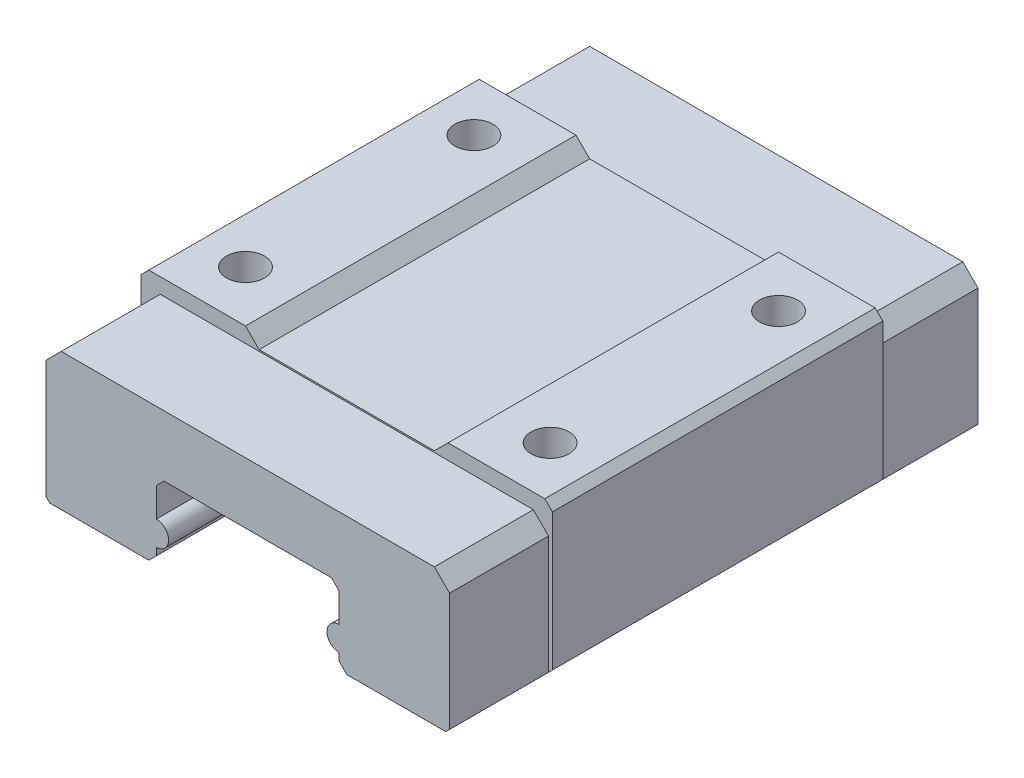
SolidWorks part; units mm, degrees
material "1023 Carbon Steel Sheet (SS)"
ref_plane "Front Plane" through (0, 0, 0) normal (0, 0, 1) x (1, 0, 0)
ref_plane "Top Plane" through (0, 0, 0) normal (0, 1, 0) x (1, 0, 0)
ref_plane "Right Plane" through (0, 0, 0) normal (1, 0, 0) x (0, 0, -1)
sketch "Master Sketch" plane through (0, 0, 0) normal (0, 1, 0) x (1, 0, 0)
  line L0 (-10, -7.5) -> (10, 7.5) construction
  line L1 (-13.25, -17.35) -> (13.25, -17.35)
  line L2 (-13.25, -17.35) -> (-13.25, 17.35)
  line L3 (-13.25, 17.35) -> (13.25, 17.35)
  line L4 (13.25, -17.35) -> (13.25, 17.35)
  line L5 (-13.25, -17.35) -> (13.25, 17.35) construction
  line L6 (-13.25, 17.35) -> (13.25, -17.35) construction
  line L7 (-13.5, -10.85) -> (13.5, -10.85)
  line L8 (-13.5, -10.85) -> (-13.5, 10.85)
  line L9 (-13.5, 10.85) -> (13.5, 10.85)
  line L10 (13.5, -10.85) -> (13.5, 10.85)
  line L11 (-13.5, -10.85) -> (13.5, 10.85) construction
  line L12 (-13.5, 10.85) -> (13.5, -10.85) construction
  point P0 (0, 0)
  point P5 (0, 0)
  point P11 (10, 7.5)
  point P12 (-10, 7.5)
  point P13 (10, -7.5)
  point P14 (-10, -7.5)
  dimension "D1" = 26.5
  dimension "D2" = 34.7
  dimension "D3" = 21.7
  dimension "D4" = 15
  dimension "D5" = 20
  dimension "D6" = 27
ref_plane "BlockMaxHeightPlane" through (0, 10, 0) normal (0, 1, 0) x (1, 0, 0)
sketch "MainBlockSketch" plane through (0, 0, 0) normal (0, 1, 0) x (1, 0, 0)
  line L0 (-13.25, -17.35) -> (13.25, -17.35) construction
  line L1 (13.25, -17.35) -> (13.25, 17.35) construction
  line L2 (-13.25, 17.35) -> (13.25, 17.35) construction
  line L3 (-13.25, -17.35) -> (-13.25, 17.35) construction
  line L4 (-13.25, -17.35) -> (13.25, -17.35)
  line L5 (13.25, -17.35) -> (13.25, 17.35)
  line L6 (-13.25, 17.35) -> (13.25, 17.35)
  line L7 (-13.25, -17.35) -> (-13.25, 17.35)
extrude "MainBlock" add sketch "MainBlockSketch" along normal blind 9
sketch "FacedSurfaceSketch" plane through (0, 0, 0) normal (0, 1, 0) x (1, 0, 0)
  line L0 (-13.5, -10.85) -> (13.5, -10.85) construction
  line L3 (-13.5, 10.85) -> (13.5, 10.85) construction
  line L4 (-13.5, -10.85) -> (13.5, -10.85)
  line L7 (-13.5, 10.85) -> (13.5, 10.85)
  line L8 (-13.5, 10.85) -> (-13.5, -10.85)
  line L9 (13.5, 10.85) -> (13.5, -10.85)
extrude "FacedSurface" add sketch "FacedSurfaceSketch" along normal up to surface (10 mm away) up to plane "BlockMaxHeightPlane"
hole_wizard "M3x0.5 Tapped Hole1" positions "Sketch4" profile "Sketch5" tap size "M3x0.5" standard "ANSI Metric"
sketch "Sketch4" plane through (0, 10, 0) normal (0, 1, 0) x (1, 0, 0)
  point P0 (-10, 7.5)
  point P3 (10, 7.5)
  point P6 (10, -7.5)
  point P9 (-10, -7.5)
sketch "Sketch5" plane through (-10, 10, -7.5) normal (1, 0, 0) x (0, 0, 1)
  line L0 (0, 0) -> (0, 9.2511)
  line L1 (0, 9.2511) -> (1.25, 8.5)
  line L2 (1.25, 8.5) -> (1.25, 0)
  line L5 (1.25, 0) -> (0, 0)
  line L10 (0, 9.2511) -> (-1.25, 8.5) construction
  line L11 (0, -6.35) -> (0, 107.95) construction
  dimension "Tap Drill Dia." = 2.5
  dimension "Tap Drill Depth" = 8.5
  dimension "Drill Angle" = 118
cosmetic thread "Hole Thread1" parameters "D1"=7, "D2"=3
cosmetic thread "Hole Thread2" parameters "D1"=7, "D2"=3
cosmetic thread "Hole Thread3" parameters "D1"=7, "D2"=3
cosmetic thread "Hole Thread4" parameters "D1"=7, "D2"=3
sketch "RailSlotSketch" plane through (0, 0, 0) normal (0, 0, 1) x (1, 0, 0)
  line L0 (-6, 2.59) -> (-6, 5)
  line L1 (-6, 0) -> (6, 0)
  line L2 (-6, 0) -> (-6, 0.99)
  line L3 (-6, 5) -> (6, 5)
  line L4 (6, 0) -> (6, 0.99)
  line L5 (-6, 0) -> (6, 5) construction
  line L6 (-6, 5) -> (6, 0) construction
  line L7 (6, 2.59) -> (6, 5)
  arc A0 (-6, 2.59) -> (-6, 0.99) centre (-6, 1.79) cw
  arc A1 (6, 2.59) -> (6, 0.99) centre (6, 1.79) ccw
  point P0 (0, 2.5)
  dimension "D3" = 0.8
  dimension "D1" = 5
  dimension "D2" = 12
  dimension "D4" = 3.21
extrude "Rail Slot" cut sketch "RailSlotSketch" against normal through all both and the other way through all
sketch "Internal Dip Sketch" plane through (0, 10, 0) normal (0, 1, 0) x (1, 0, 0)
  line L1 (6.75, -10.85) -> (-6.75, -10.85)
  line L2 (6.75, -10.85) -> (6.75, 10.85)
  line L3 (6.75, 10.85) -> (-6.75, 10.85)
  line L4 (-6.75, -10.85) -> (-6.75, 10.85)
  line L5 (6.75, -10.85) -> (-6.75, 10.85) construction
  line L6 (6.75, 10.85) -> (-6.75, -10.85) construction
  line L7 (-13.5, 10.85) -> (13.5, 10.85) construction
  line L8 (-13.25, 7.5) -> (-6.75, 7.5) construction
  line L9 (-13.25, -17.35) -> (-13.25, 17.35) construction
  point P10 (-10, 7.5)
extrude "Internal Dip" cut sketch "Internal Dip Sketch" against normal blind 0.9
chamfer "Internal Chamfer" distance 0.5 angle 45 2 edges at (6, 5, 0) (-6, 5, 0)
chamfer "Cosmetic Chamfers" distance 1 angle 45 6 edges at (-6.75, 9.1, 0) (6.75, 9.1, 0) (13.25, 9, 14.1) (-13.25, 9, 14.1) (-13.25, 9, -14.1) (13.25, 9, -14.1)
chamfer "Smaller Cosmetic Chamfers" distance 0.5 angle 45 6 edges at (13.5, 10, 0) (-13.5, 10, 0) (-13.5, 0, 0) (13.5, 0, 0) (6, 0, 0) (-6, 0, 0)
